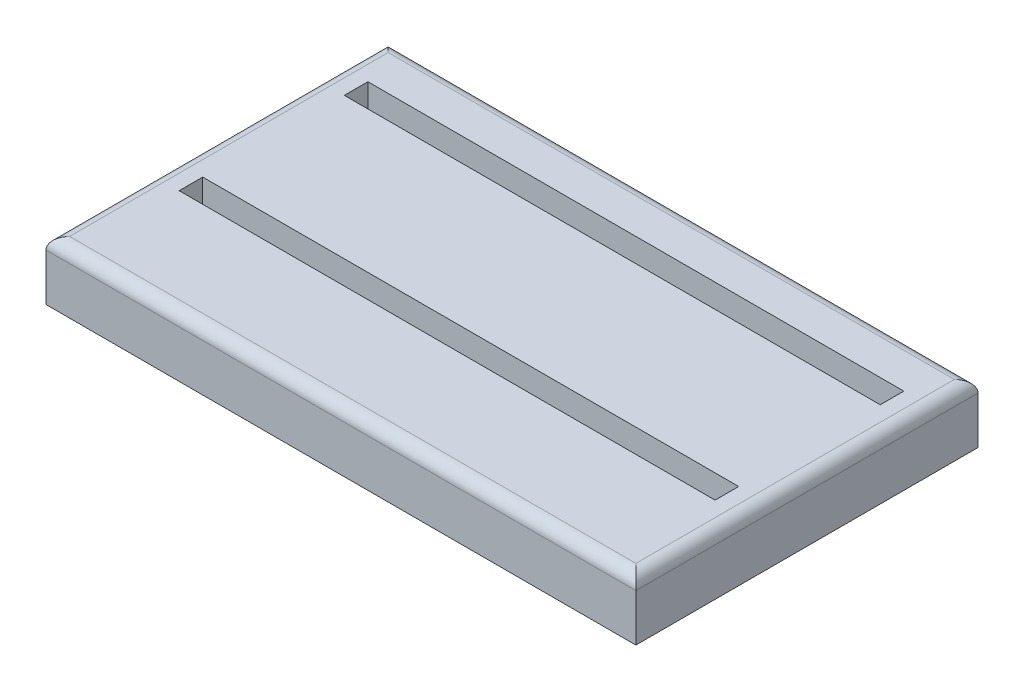
SolidWorks part; units mm, degrees
ref_plane "Front Plane" through (0, 0, 0) normal (0, 0, 1) x (1, 0, 0)
ref_plane "Top Plane" through (0, 0, 0) normal (0, 1, 0) x (1, 0, 0)
ref_plane "Right Plane" through (0, 0, 0) normal (1, 0, 0) x (0, 0, -1)
sketch "Sketch2" plane through (0, 0, 0) normal (0, 1, 0) x (1, 0, 0)
  line L0 (0, 242.4303) -> (0, -237.7501) construction
  line L1 (-63.5, 30.48) -> (-63.5, -43.18)
  line L2 (-63.5, 30.48) -> (63.5, 30.48)
  line L3 (-63.5, -43.18) -> (63.5, -43.18)
  line L4 (63.5, 30.48) -> (63.5, -43.18)
  dimension "D1" = 127
  dimension "D2" = 63.5
  dimension "D3" = 73.66
  dimension "D4" = 43.18
extrude "Boss-Extrude1" add sketch "Sketch2" along normal blind 12.7
fillet "Fillet1" radius 2.54 4 edges at (63.5, 12.7, 6.35) (-63.5, 12.7, 6.35) (0, 12.7, 43.18) (0, 12.7, -30.48)
sketch "Sketch3" plane through (0, 12.7, 0) normal (0, 1, 0) x (1, 0, 0)
  line L0 (57.6928, 15.24) -> (57.6928, 20.32)
  line L1 (57.6928, 15.24) -> (-57.6928, 15.24)
  line L2 (57.6928, 20.32) -> (-57.6928, 20.32)
  line L3 (-57.6928, 15.24) -> (-57.6928, 20.32)
  line L5 (63.5, 30.48) -> (63.5, -43.18) construction
  line L6 (-63.5, 30.48) -> (63.5, 30.48) construction
  line L7 (-60.96, -40.64) -> (60.96, -40.64) construction
  line L10 (57.6928, -15.24) -> (57.6928, -20.32)
  line L11 (57.6928, -20.32) -> (-57.6928, -20.32)
  line L12 (-57.6928, -15.24) -> (-57.6928, -20.32)
  line L13 (57.6928, -15.24) -> (-57.6928, -15.24)
  dimension "D1" = 115.3856
  dimension "D2" = 5.8072
  dimension "D3" = 10.16
  dimension "D4" = 5.08
  dimension "D5" = 20.32
extrude "Cut-Extrude1" cut sketch "Sketch3" against normal blind 12.7
